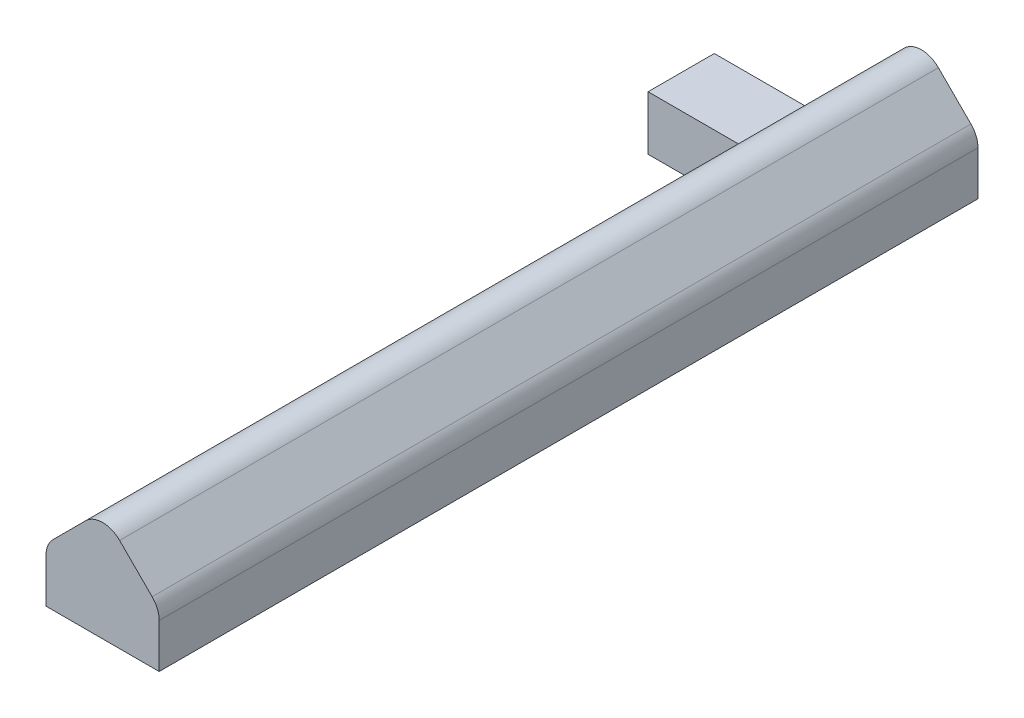
SolidWorks part; units mm, degrees
ref_plane "Płaszczyzna przednia" through (0, 0, 0) normal (0, 0, 1) x (1, 0, 0)
ref_plane "Płaszczyzna górna" through (0, 0, 0) normal (0, 1, 0) x (1, 0, 0)
ref_plane "Płaszczyzna prawa" through (0, 0, 0) normal (1, 0, 0) x (0, 0, -1)
sketch "Szkic1" plane through (0, 0, 0) normal (0, 0, 1) x (1, 0, 0)
  line L0 (0, 0) -> (0, 9.4056) construction
  line L1 (-4.7, 2.25) -> (4.7, 2.25)
  line L2 (-4.7, 2.25) -> (-4.7, -2.25)
  line L3 (-4.7, -2.25) -> (4.7, -2.25)
  line L4 (4.7, 2.25) -> (4.7, -2.25)
  line L5 (-4.7, 2.25) -> (4.7, -2.25) construction
  line L6 (-4.7, -2.25) -> (4.7, 2.25) construction
  line L7 (-4.7, 2.25) -> (0, 6.95)
  line L8 (0, 6.95) -> (4.7, 2.25)
  point P0 (0, 0)
  dimension "D1" = 9.4
  dimension "D2" = 4.5
  dimension "D3" = 45
extrude "Dodanie-wyciągnięcie1" add sketch "Szkic1" along normal blind 68 contours L8 L7 L1 | L4 L1 L2 L3 region at (0, 3.8167, 0) region at (0, 0, 0)
sketch "Szkic2" plane through (0, -2.25, 0) normal (0, -1, 0) x (1, 0, 0)
  line L0 (0, 0) -> (0, 68) construction
  line L1 (-4.7, 0) -> (4.7, 0) construction
  line L2 (-4.7, 68) -> (4.7, 68) construction
  line L3 (4.7, 68) -> (4.7, 0) construction
  line L8 (-10, 43) -> (-10, 50)
  line L9 (0, 50) -> (-10, 50)
  line L10 (0, 43) -> (0, 50)
  line L11 (0, 43) -> (-10, 43)
  line L12 (-1.5, 50) -> (-1.5, 43)
  line L13 (-4.7, 68) -> (0, 68) construction
  line M6 (4.7, 0) -> (4.7, 68)
  line M8 (-4.7, 68) -> (-4.7, 0)
  dimension "D1" = 6.2
  dimension "D2" = 14.7
  dimension "D3" = 7
  dimension "D4" = 18
extrude "Wytnij-wyciągnięcie1" cut sketch "Szkic2" against normal blind 10 contours M6 | L12 L9 L11 M8 region at (-3.1, -2.25, 46.5)
ref_plane "Płaszczyzna1" through (-22.5, 11.75, 5) normal (0, -1, 0) x (-1, 0, 0)
sketch "Szkic4" plane through (0, -2.25, 0) normal (0, -1, 0) x (1, 0, 0)
  line L0 (0, 0) -> (0, 5) construction
  line L2 (-4.7, 0) -> (4.7, 0) construction
  line L3 (0, 0) -> (0, -7.3747) construction
  line L9 (7.5, -5) -> (-7.5, -5)
  line L10 (7.5, -5) -> (7.5, 5)
  line L11 (7.5, 5) -> (-7.5, 5)
  line L12 (-7.5, -5) -> (-7.5, 5)
  line L13 (7.5, -5) -> (-7.5, 5) construction
  line L14 (7.5, 5) -> (-7.5, -5) construction
  line L15 (13.1781, -10) -> (-13.1781, -10)
  line L16 (13.1781, -10) -> (13.1781, -5)
  line L17 (13.1781, -5) -> (-13.1781, -5)
  line L18 (-13.1781, -10) -> (-13.1781, -5)
  line L19 (13.1781, -10) -> (-13.1781, -5) construction
  line L20 (13.1781, -5) -> (-13.1781, -10) construction
  point P4 (0, 0)
  point P10 (0, -7.5)
  dimension "D1" = 5
  dimension "D2" = 15
  dimension "D3" = 10
  dimension "D4" = 5
fillet "Zaokrąglenie1" radius 2 3 edges at (4.7, 2.25, 34) (-4.7, 2.25, 59) (0, 6.95, 34)
sketch "Szkic5" plane through (0, -2.25, 0) normal (0, -1, 0) x (1, 0, 0)
  line L0 (-4.7, 68) -> (-4.7, 50) construction
  line L1 (-4.7, 5) -> (-12.2, 5)
  line L2 (-4.7, 5) -> (-4.7, 10.5)
  line L3 (-4.7, 10.5) -> (-12.2, 10.5)
  line L4 (-12.2, 5) -> (-12.2, 10.5)
  line L5 (-8.45, 10.5) -> (-8.45, 5) construction
  line L6 (-4.7, 7.75) -> (-12.2, 7.75) construction
  line L7 (-4.7, 0) -> (4.7, 0) construction
  line L8 (-4.7, 68) -> (-4.7, 50) construction
  point P196 (-8.45, 7.75)
  dimension "D1" = 5.5
  dimension "D2" = 7.5
  dimension "D3" = 5
extrude "Dodanie-wyciągnięcie4" add sketch "Szkic5" against normal up to vertex (4.5 mm away) up to point (-4.7, 2.25, 43)
